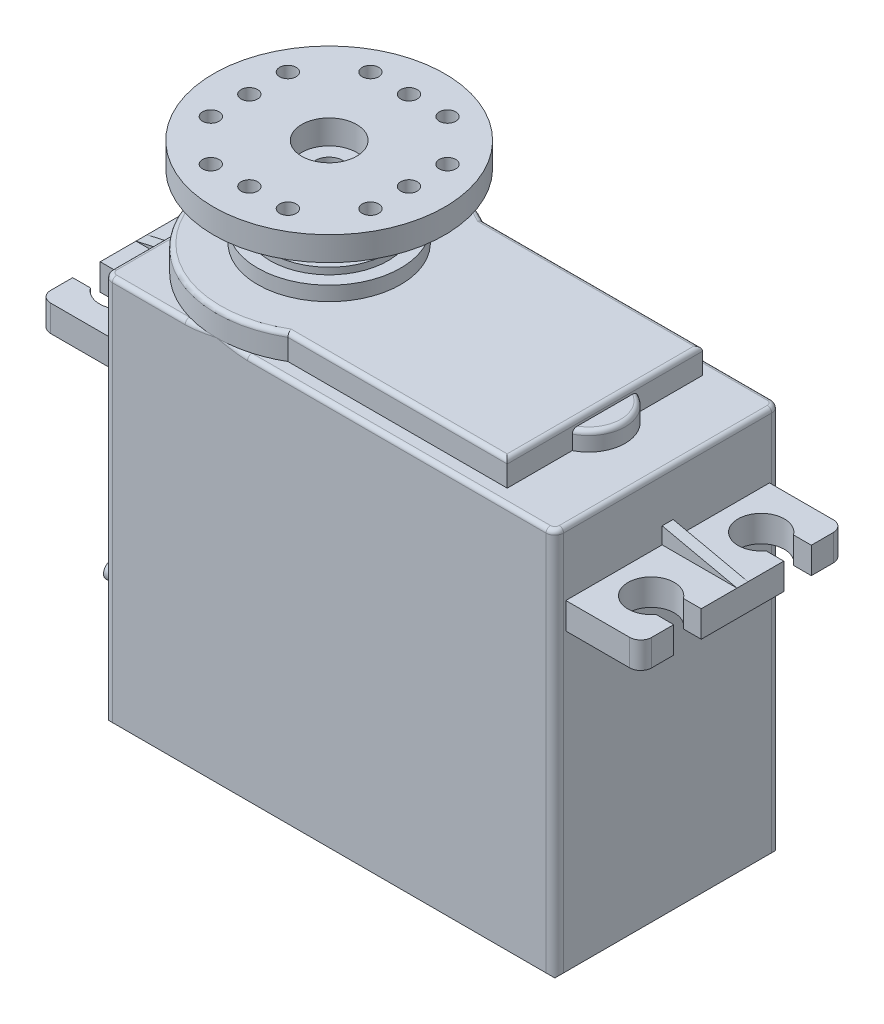
SolidWorks part; units mm, degrees
ref_plane "Front Plane" through (0, 0, 0) normal (0, 0, 1) x (1, 0, 0)
ref_plane "Top Plane" through (0, 0, 0) normal (0, 1, 0) x (1, 0, 0)
ref_plane "Right Plane" through (0, 0, 0) normal (1, 0, 0) x (0, 0, -1)
sketch "Sketch1" plane through (0, 0, 0) normal (0, 1, 0) x (1, 0, 0)
  line L1 (-20.5, -10.25) -> (20.5, -10.25)
  line L2 (-20.5, -10.25) -> (-20.5, 10.25)
  line L3 (-20.5, 10.25) -> (20.5, 10.25)
  line L4 (20.5, -10.25) -> (20.5, 10.25)
  line L5 (-20.5, -10.25) -> (20.5, 10.25) construction
  line L6 (-20.5, 10.25) -> (20.5, -10.25) construction
  point P0 (0, 0)
  dimension "D1" = 41
  dimension "D2" = 20.5
extrude "Boss-Extrude1" add sketch "Sketch1" along normal blind 37
sketch "Sketch2" plane through (0, 37, 0) normal (0, 1, 0) x (1, 0, 0)
  line L0 (-20.5, 10.25) -> (-20.5, -10.25) construction
  line L1 (20.5, -10.25) -> (20.5, 10.25) construction
  line L2 (-5.122, -8.875) -> (14.8, -8.875)
  line L4 (-5.122, 8.875) -> (14.8, 8.875)
  line L5 (14.8, -8.875) -> (14.8, -2.9672)
  line L9 (14.8, 2.9672) -> (14.8, 8.875)
  arc A0 (-5.122, 8.875) -> (-5.122, -8.875) centre (-10.25, 0) ccw
  arc A1 (14.8, -2.9672) -> (14.8, 2.9672) centre (13.3208, 0) ccw
  point P5 (4.4919, 0)
  dimension "D1" = 10.25
  dimension "D2" = 17.75
  dimension "D3" = 5.7
extrude "Boss-Extrude2" add sketch "Sketch2" along normal blind 2.3
sketch "Sketch3" plane through (0, 39.3, 0) normal (0, 1, 0) x (1, 0, 0)
  circle A0 centre (-10.25, 0) radius 6.5
  dimension "D1" = 13
extrude "Boss-Extrude3" add sketch "Sketch3" along normal blind 1.3
sketch "Sketch4" plane through (0, 40.6, 0) normal (0, 1, 0) x (1, 0, 0)
  circle A0 centre (-10.25, 0) radius 5.35
  dimension "D1" = 10.7
extrude "Boss-Extrude4" add sketch "Sketch4" along normal blind 0.6
sketch "Sketch5" plane through (0, 39.3, 0) normal (0, 1, 0) x (1, 0, 0)
  line L0 (14.8, 2.9672) -> (14.8, -2.9672)
  arc A0 (14.8, -2.9672) -> (14.8, 2.9672) centre (13.3208, 0) ccw construction
  arc A1 (14.8, -2.9672) -> (14.8, 2.9672) centre (13.3208, 0) ccw
extrude "Cut-Extrude1" cut sketch "Sketch5" against normal blind 0.6
sketch "Sketch6" plane through (0, 41.2, 0) normal (0, 1, 0) x (1, 0, 0)
  circle A0 centre (-10.25, 0) radius 3
  dimension "D1" = 6
extrude "Boss-Extrude5" add sketch "Sketch6" along normal blind 4
chamfer "Chamfer1" distance 2 angle 45 4 edges at (-20.5, 0, 0) (0, 0, -10.25) (20.5, 0, 0) (0, 0, 10.25)
fillet "Fillet2" radius 0.8 4 edges at (-20.5, 19.5, -10.25) (-20.5, 19.5, 10.25) (20.5, 19.5, -10.25) (20.5, 19.5, 10.25)
sketch "Sketch7" plane through (-20.5, 0, 0) normal (-1, 0, 0) x (0, 0, 1)
  line L1 (-9.25, 31.2) -> (9.25, 31.2)
  line L2 (-9.25, 31.2) -> (-9.25, 28.8)
  line L3 (-9.25, 28.8) -> (9.25, 28.8)
  line L4 (9.25, 31.2) -> (9.25, 28.8)
  line L6 (-9.45, 37) -> (0, 37) construction
  line L9 (-10.25, 37) -> (-10.25, 2) construction
  dimension "D1" = 5.8
  dimension "D2" = 2.4
  dimension "D3" = 18.5
  dimension "D4" = 1
extrude "Boss-Extrude6" add sketch "Sketch7" along normal blind 6.8
sketch "Sketch9" plane through (0, 31.2, 0) normal (0, 1, 0) x (1, 0, 0)
  line L0 (-27.3, -9.25) -> (-27.3, 9.25) construction
  line L3 (-25.6875, 6.25) -> (-27.3, 6.25)
  line L4 (-21.6, 3.75) -> (-22.3125, 3.75)
  line L5 (-21.6, 3.75) -> (-21.6, 6.25)
  line L6 (-21.6, 6.25) -> (-22.3125, 6.25)
  line L7 (-27.3, 3.75) -> (-27.3, 6.25)
  line L8 (-21.6, 3.75) -> (-24, 5) construction
  line L9 (-21.6, 6.25) -> (-24, 5) construction
  line L10 (-21.6, -6.25) -> (-27.3, -6.25)
  line L11 (-21.6, -6.25) -> (-21.6, -3.75)
  line L12 (-21.6, -3.75) -> (-27.3, -3.75)
  line L13 (-27.3, -6.25) -> (-27.3, -3.75)
  line L14 (-21.6, -6.25) -> (-24, -5) construction
  line L15 (-21.6, -3.75) -> (-24, -5) construction
  line L18 (-25.6875, 3.75) -> (-27.3, 3.75)
  arc A0 (-25.6875, 3.75) -> (-25.6875, 6.25) centre (-24, 5) ccw
  arc A1 (-25.6875, -6.25) -> (-25.6875, -3.75) centre (-24, -5) ccw
  line M4 (-27.3, 9.25) -> (-27.3, -9.25)
  dimension "D1" = 4.2
  dimension "D2" = 4.2
  dimension "D3" = 3.3
  dimension "D4" = 10
  dimension "D5" = 5
  dimension "D6" = 2.5
  dimension "D7" = 2.5
  dimension "D8" = 3.3
extrude "Cut-Extrude2" cut sketch "Sketch9" against normal blind 6.8 contours A0 L3 L18 M4 | L12 A1 | L10 A1 | L10 A1 L12 M4 region at (-24.5093, 31.2, -5) region at (-24.6644, 31.2, 5) region at (-24, 31.2, 3.4033) region at (-24, 31.2, 6.5967)
fillet "Fillet1" radius 1 2 edges at (-27.3, 30, 9.25) (-27.3, 30, -9.25)
sketch "Sketch10" plane through (0, 31.2, 0) normal (0, 1, 0) x (1, 0, 0)
  line L0 (-20.5, -9.25) -> (-20.5, 9.25) construction
  line L1 (-27.3, -0.5) -> (-20.5, -0.5)
  line L2 (-27.3, -0.5) -> (-27.3, 0.5)
  line L3 (-27.3, 0.5) -> (-20.5, 0.5)
  line L4 (-20.5, -0.5) -> (-20.5, 0.5)
  line L5 (-27.3, -0.5) -> (-20.5, 0.5) construction
  line L6 (-27.3, 0.5) -> (-20.5, -0.5) construction
  line L7 (-27.3, -3.75) -> (-27.3, 3.75) construction
  point P0 (-23.9, 0)
  dimension "D1" = 1
extrude "Boss-Extrude7" add sketch "Sketch10" along normal blind 1.5
sketch "Sketch11" plane through (0, 0, 0.5) normal (0, 0, 1) x (1, 0, 0)
  line L0 (-27.3, 31.2) -> (-20.5, 32.7)
  line L1 (-20.5, 32.7) -> (-27.3, 32.7)
  line L2 (-27.3, 32.7) -> (-27.3, 31.2)
extrude "Cut-Extrude3" cut sketch "Sketch11" against normal blind 1.5
ref_plane "Plane1" through (0, 0, 0) normal (-1, 0, 0) x (0, 0, 1)
mirror "Mirror2" about plane through (0, 0, 0) normal (-1, 0, 0) of "Cut-Extrude3", "Boss-Extrude7", "Fillet1", "Cut-Extrude2", "Boss-Extrude6"
sketch "Sketch12" plane through (0, 45.2, 0) normal (0, 1, 0) x (1, 0, 0)
  circle A0 centre (-10.25, 0) radius 1.25
  dimension "D1" = 2.5
extrude "Cut-Extrude4" cut sketch "Sketch12" against normal blind 4
fillet "Fillet5" radius 0.4 5 edges at (16.6363, 38.7, 0) (14.8, 39.3, 0) (4.839, 39.3, -8.875) (-20.5, 39.3, 0) (4.839, 39.3, 8.875)
fillet "Fillet7" radius 0.4 11 edges at (20.2657, 37, 10.0157) (4.725, 37, 10.25) (-14.975, 37, 10.25) (-20.2657, 37, 10.0157) (-20.5, 37, 4.725) (-20.5, 37, -4.725) (-20.2657, 37, -10.0157) (-14.975, 37, -10.25) (4.725, 37, -10.25) (20.2657, 37, -10.0157) (20.5, 37, 0)
sketch "Sketch13" plane through (-20.5, 0, 0) normal (-1, 0, 0) x (0, 0, 1)
  line L0 (8.25, 0) -> (-8.25, 0) construction
  line L1 (-3.5, 3.2) -> (3.5, 3.2)
  line L2 (-3.5, 3.2) -> (-3.5, 7.4)
  line L3 (-3.5, 7.4) -> (3.5, 7.4)
  line L4 (3.5, 3.2) -> (3.5, 7.4)
  line L5 (-3.5, 3.2) -> (3.5, 7.4) construction
  line L6 (-3.5, 7.4) -> (3.5, 3.2) construction
  point P0 (0, 5.3)
  dimension "D1" = 7
  dimension "D2" = 4.2
  dimension "D3" = 3.2
extrude "Boss-Extrude8" add sketch "Sketch13" along normal blind 1
sketch "Sketch14" plane through (-21.5, 0, 0) normal (-1, 0, 0) x (0, 0, 1)
  line L9 (3.15, 3.55) -> (3.15, 7.05)
  line L10 (3.15, 7.05) -> (-3.15, 7.05)
  line L11 (-3.15, 7.05) -> (-3.15, 3.55)
  line L12 (-3.15, 3.55) -> (3.15, 3.55)
  line L13 (3.15, 3.55) -> (3.15, 7.05)
  line L14 (3.15, 7.05) -> (-3.15, 7.05)
  line L15 (-3.15, 7.05) -> (-3.15, 3.55)
  line L16 (-3.15, 3.55) -> (3.15, 3.55)
  dimension "D1" = 0.35
extrude "Boss-Extrude9" add sketch "Sketch14" along normal blind 4 draft 5 contours L14 L15 L16 L13
sketch "Sketch15" plane through (-25.5, 0, 0) normal (-1, 0, 0) x (0, 0, 1)
  line L0 (-2.8, 3.9) -> (2.8, 3.9) construction
  circle A0 centre (-1.5, 5.3) radius 0.75
  circle A1 centre (0, 5.3) radius 0.75
  circle A2 centre (1.5, 5.3) radius 0.75
  dimension "D1" = 1.5
  dimension "D2" = 1.5
  dimension "D3" = 1.5
  dimension "D4" = 1.4
extrude "Boss-Extrude12" add sketch "Sketch15" along normal blind 3 separate body contours A0 | A1 | A2 region at (-25.5, 5.3, -1.5) region at (-25.5, 5.3, 1.5) region at (-25.5, 5.3, 0)
sketch "Sketch16" plane through (0, 45.2, 0) normal (0, 1, 0) x (1, 0, 0)
  circle A0 centre (-10.25, 0) radius 10.5
  dimension "D1" = 21
extrude "Boss-Extrude13" add sketch "Sketch16" along normal blind 2.2
sketch "Sketch17" plane through (0, 47.4, 0) normal (0, 1, 0) x (1, 0, 0)
  circle A0 centre (-17.5, 0) radius 0.75
  circle A18 centre (-17.5, 3.5) radius 0.75
  circle A19 centre (-17.5, -3.5) radius 0.75
  circle A20 centre (-10.25, 7.25) radius 0.75
  circle A21 centre (-6.75, 7.25) radius 0.75
  circle A22 centre (-13.75, 7.25) radius 0.75
  circle A23 centre (-3, 0) radius 0.75
  circle A24 centre (-3, -3.5) radius 0.75
  circle A25 centre (-3, 3.5) radius 0.75
  circle A26 centre (-10.25, -7.25) radius 0.75
  circle A27 centre (-13.75, -7.25) radius 0.75
  circle A28 centre (-6.75, -7.25) radius 0.75
  circle A29 centre (-10.25, 0) radius 2.5
  point P3 (-10.25, 0)
  point P29 (-10.25, 0)
  point P42 (-10.25, 0)
  dimension "D1" = 7.25
  dimension "D2" = 1.5
  dimension "D3" = 1.5
  dimension "D4" = 1.5
  dimension "D8" = 5
  dimension "D5" = 3.5
  dimension "D6" = 3.5
  dimension "D7" = 4
extrude "Cut-Extrude5" cut sketch "Sketch17" against normal up to surface (2.2 mm away) up to face at (-10.25, 45.2, 3)
